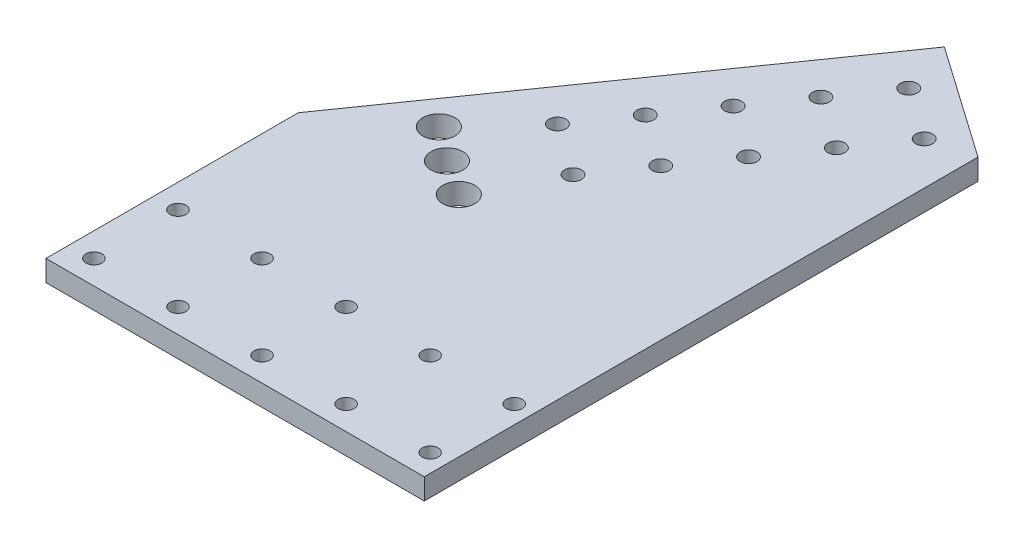
SolidWorks part; units mm, degrees
material "6061-T6 (SS)"
ref_plane "Front Plane" through (0, 0, 0) normal (0, 0, 1) x (1, 0, 0)
ref_plane "Top Plane" through (0, 0, 0) normal (0, 1, 0) x (1, 0, 0)
ref_plane "Right Plane" through (0, 0, 0) normal (1, 0, 0) x (0, 0, -1)
sketch "Sketch1" plane through (0, 0, 0) normal (0, 1, 0) x (1, 0, 0)
  line L5 (0, 0) -> (114.3, 0)
  line L6 (0, 0) -> (0, 203.2)
  line L7 (0, 203.2) -> (114.3, 203.2)
  line L8 (114.3, 0) -> (114.3, 203.2)
  dimension "D1" = 203.2
  dimension "D2" = 114.3
extrude "Boss-Extrude1" add sketch "Sketch1" along normal blind 6.35
sketch "Sketch2" plane through (0, 6.35, 0) normal (0, 1, 0) x (1, 0, 0)
  line L0 (0, 0) -> (114.3, 0) construction
  line L1 (0, 203.2) -> (0, 0) construction
  line L2 (114.3, 0) -> (114.3, 203.2) construction
  line L5 (-55, 0) -> (55, 0) construction
  circle A0 centre (7.239, 7.239) radius 2.413
  circle A2 centre (7.239, 32.639) radius 2.413
  circle A3 centre (32.639, 32.639) radius 2.413
  circle A4 centre (58.039, 32.639) radius 2.413
  circle A5 centre (83.439, 32.639) radius 2.413
  circle A6 centre (108.839, 32.639) radius 2.413
  circle A7 centre (32.639, 7.239) radius 2.413
  circle A8 centre (58.039, 7.239) radius 2.413
  circle A9 centre (83.439, 7.239) radius 2.413
  circle A10 centre (108.839, 7.239) radius 2.413
  dimension "D1" = 4.826
  dimension "D2" = 7.239
  dimension "D3" = 7.239
  dimension "D6" = 25.4
  dimension "D7" = 7.239
  dimension "D8" = 5.461
  dimension "D4" = 2
  dimension "D5" = 5
extrude "Cut-Extrude1" cut sketch "Sketch2" against normal through all
sketch "Sketch5" plane through (0, 0, 0) normal (0, -1, 0) x (-1, 0, 0)
  line L0 (-88.9, 203.2) -> (0, 76.2376)
  line L1 (-114.3, 203.2) -> (0, 203.2) construction
  line L3 (0, 76.2376) -> (0, 203.2)
  line L4 (0, 203.2) -> (-88.9, 203.2)
  dimension "D1" = 55
  dimension "D2" = 88.9
extrude "Cut-Extrude4" cut sketch "Sketch5" against normal through all
sketch "Sketch3" plane through (0, 6.35, 0) normal (0, 1, 0) x (1, 0, 0)
  line L0 (90.481, 148.3438) -> (68.6278, 117.1341) construction
  line L1 (88.9, 203.2) -> (0, 76.2376) construction
  line L2 (114.3, 0) -> (114.3, 203.2) construction
  line L3 (90.481, 148.3438) -> (70.7879, 162.1331) construction
  circle A0 centre (90.481, 148.3438) radius 2.5527
  circle A1 centre (74.8762, 159.2704) radius 2.5527
  circle A3 centre (63.9496, 143.6655) radius 2.5527
  circle A4 centre (79.5544, 132.7389) radius 2.5527
  circle A6 centre (68.6278, 117.1341) radius 2.5527
  circle A7 centre (53.0229, 128.0607) radius 2.5527
  circle A8 centre (42.0963, 112.4558) radius 2.5527
  circle A9 centre (57.7011, 101.5292) radius 2.5527
  circle A10 centre (85.8028, 174.8752) radius 2.5527
  circle A11 centre (101.4077, 163.9486) radius 2.5527
  dimension "D1" = 5.1054
  dimension "D2" = 32.7594
  dimension "D4" = 19.05
  dimension "D5" = 23.819
  dimension "D6" = 5.1054
  dimension "D7" = 19.05
  dimension "D9" = 19.05
  dimension "D10" = 5.1054
  dimension "D11" = 19.05
  dimension "D12" = 19.05
  dimension "D13" = 5.1054
  dimension "D14" = 5.1054
  dimension "D15" = 19.05
  dimension "D16" = 19.05
  dimension "D17" = 19.05
  dimension "D18" = 32.7594
  dimension "D3" = 3
  dimension "D8" = 4
extrude "Cut-Extrude2" cut sketch "Sketch3" against normal through all
sketch "Sketch6" plane through (0, 6.35, 0) normal (0, 1, 0) x (1, 0, 0)
  line L0 (0, 0) -> (114.3, 0) construction
  line L2 (0, 76.2376) -> (0, 0) construction
  circle A0 centre (24.9267, 93.7768) radius 4.826
  circle A4 centre (35.0484, 86.106) radius 4.826
  circle A5 centre (45.6386, 79.0962) radius 4.826
  circle A6 centre (68.6278, 117.1341) radius 2.5527 construction
  circle A7 centre (68.5706, 117.1741) radius 2.5527 construction
  dimension "D1" = 9.652
  dimension "D2" = 24.9267
  dimension "D3" = 9.652
  dimension "D4" = 9.652
  dimension "D5" = 12.7
  dimension "D6" = 12.7
  dimension "D7" = 45.72
  dimension "D8" = 44.45
  dimension "D9" = 86.106
extrude "Cut-Extrude5" cut sketch "Sketch6" against normal through all
sketch "Sketch7" plane through (0, 6.35, 0) normal (0, 1, 0) x (1, 0, 0)
  line L0 (80.4003, 191.0612) -> (114.3, 167.3244)
  line L1 (88.9, 203.2) -> (0, 76.2376) construction
  line L2 (114.3, 0) -> (114.3, 203.2) construction
  line L3 (114.3, 167.3244) -> (114.3, 203.2)
  line L4 (114.3, 203.2) -> (88.9, 203.2)
  line L5 (88.9, 203.2) -> (80.4003, 191.0612)
  circle A0 centre (101.4077, 163.9486) radius 2.5527 construction
  dimension "D1" = 10.16
extrude "Cut-Extrude6" cut sketch "Sketch7" against normal through all
